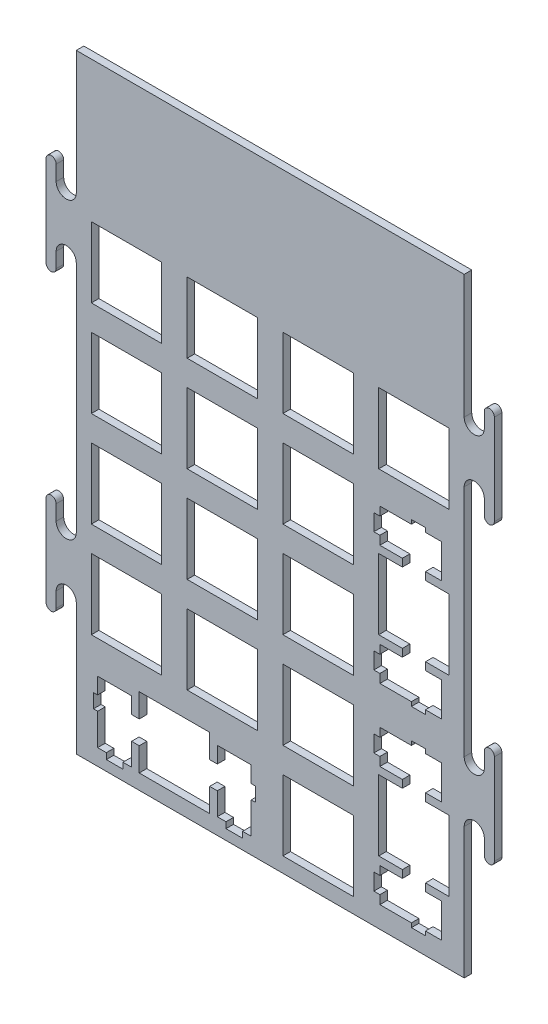
SolidWorks part; units mm, degrees
ref_plane "前视基准面" through (0, 0, 0) normal (0, 0, 1) x (1, 0, 0)
ref_plane "上视基准面" through (0, 0, 0) normal (0, 1, 0) x (1, 0, 0)
ref_plane "右视基准面" through (0, 0, 0) normal (1, 0, 0) x (0, 0, -1)
other "Configuration Table"
sketch "Model" plane through (0, 0, 0) normal (0, 0, 1) x (1, 0, 0)
  line L0 (114.6852, 14.7846) -> (114.6852, 10.0841)
  line L1 (114.6852, 10.0841) -> (113.1597, 10.0841)
  line L2 (113.1597, 10.0841) -> (113.1597, 13.3143)
  line L3 (113.1597, 13.3143) -> (106.4101, 13.3143)
  line L4 (106.4101, 13.3143) -> (106.4101, 10.0841)
  line L5 (106.4101, 10.0841) -> (105.5846, 10.0841)
  line L6 (105.5846, 10.0841) -> (105.5846, 7.2853)
  line L7 (105.5846, 7.2853) -> (106.4101, 7.2853)
  line L8 (106.4101, 7.2853) -> (106.4101, 1.0153)
  line L9 (106.4101, 1.0153) -> (108.1354, 1.0153)
  line L10 (108.1354, 1.0153) -> (108.1354, -0.185)
  line L11 (108.1354, -0.185) -> (111.4344, -0.185)
  line L12 (111.4344, -0.185) -> (111.4344, 1.0153)
  line L13 (111.4344, 1.0153) -> (113.1597, 1.0153)
  line L14 (113.1597, 1.0153) -> (113.1597, 5.4842)
  line L15 (113.1597, 5.4842) -> (114.6852, 5.4842)
  line L16 (114.6852, 5.4842) -> (114.6852, 0.7851)
  line L17 (114.6852, 0.7851) -> (128.6846, 0.7851)
  line L18 (128.6846, 0.7851) -> (128.6846, 5.4842)
  line L19 (128.6846, 5.4842) -> (130.2101, 5.4842)
  line L20 (130.2101, 5.4842) -> (130.2101, 1.0153)
  line L21 (130.2101, 1.0153) -> (131.9354, 1.0153)
  line L22 (131.9354, 1.0153) -> (131.9354, -0.185)
  line L23 (131.9354, -0.185) -> (135.2345, -0.185)
  line L24 (135.2345, -0.185) -> (135.2345, 1.0153)
  line L25 (135.2345, 1.0153) -> (136.9598, 1.0153)
  line L26 (136.9598, 1.0153) -> (136.9598, 7.2853)
  line L27 (136.9598, 7.2853) -> (137.7852, 7.2853)
  line L28 (137.7852, 7.2853) -> (137.7852, 10.0841)
  line L29 (137.7852, 10.0841) -> (136.9598, 10.0841)
  line L30 (136.9598, 10.0841) -> (136.9598, 13.3143)
  line L31 (136.9598, 13.3143) -> (130.2101, 13.3143)
  line L32 (130.2101, 13.3143) -> (130.2101, 10.0841)
  line L33 (130.2101, 10.0841) -> (128.6846, 10.0841)
  line L34 (128.6846, 10.0841) -> (128.6846, 14.7846)
  line L35 (128.6846, 14.7846) -> (114.6852, 14.7846)
  line L36 (143.2602, 14.7846) -> (157.2595, 14.7846)
  line L37 (157.2595, 14.7846) -> (157.2595, 0.7851)
  line L38 (157.2595, 0.7851) -> (143.2602, 0.7851)
  line L39 (143.2602, 0.7851) -> (143.2602, 14.7846)
  line L40 (168.8105, 33.4102) -> (168.8105, 32.5848)
  line L41 (168.8105, 32.5848) -> (162.5402, 32.5848)
  line L42 (162.5402, 32.5848) -> (162.5402, 30.8594)
  line L43 (162.5402, 30.8594) -> (161.3401, 30.8594)
  line L44 (161.3401, 30.8594) -> (161.3401, 27.5604)
  line L45 (161.3401, 27.5604) -> (162.5402, 27.5604)
  line L46 (162.5402, 27.5604) -> (162.5402, 25.8351)
  line L47 (162.5402, 25.8351) -> (167.0106, 25.8351)
  line L48 (167.0106, 25.8351) -> (167.0106, 24.3096)
  line L49 (167.0106, 24.3096) -> (162.3102, 24.3096)
  line L50 (162.3102, 24.3096) -> (162.3102, 10.3101)
  line L51 (162.3102, 10.3101) -> (167.0106, 10.3101)
  line L52 (167.0106, 10.3101) -> (167.0106, 8.7846)
  line L53 (167.0106, 8.7846) -> (162.5402, 8.7846)
  line L54 (162.5402, 8.7846) -> (162.5402, 7.0594)
  line L55 (162.5402, 7.0594) -> (161.3401, 7.0594)
  line L56 (161.3401, 7.0594) -> (161.3401, 3.7603)
  line L57 (161.3401, 3.7603) -> (162.5402, 3.7603)
  line L58 (162.5402, 3.7603) -> (162.5402, 2.035)
  line L59 (162.5402, 2.035) -> (168.8105, 2.035)
  line L60 (168.8105, 2.035) -> (168.8105, 1.2096)
  line L61 (168.8105, 1.2096) -> (171.6105, 1.2096)
  line L62 (171.6105, 1.2096) -> (171.6105, 2.035)
  line L63 (171.6105, 2.035) -> (174.8405, 2.035)
  line L64 (174.8405, 2.035) -> (174.8405, 8.7846)
  line L65 (174.8405, 8.7846) -> (171.6105, 8.7846)
  line L66 (171.6105, 8.7846) -> (171.6105, 10.3101)
  line L67 (171.6105, 10.3101) -> (176.3095, 10.3101)
  line L68 (176.3095, 10.3101) -> (176.3095, 24.3096)
  line L69 (176.3095, 24.3096) -> (171.6105, 24.3096)
  line L70 (171.6105, 24.3096) -> (171.6105, 25.8351)
  line L71 (171.6105, 25.8351) -> (174.8405, 25.8351)
  line L72 (174.8405, 25.8351) -> (174.8405, 32.5848)
  line L73 (174.8405, 32.5848) -> (171.6105, 32.5848)
  line L74 (171.6105, 32.5848) -> (171.6105, 33.4102)
  line L75 (171.6105, 33.4102) -> (168.8105, 33.4102)
  line L76 (105.1602, 33.8345) -> (119.1597, 33.8345)
  line L77 (119.1597, 33.8345) -> (119.1597, 19.8351)
  line L78 (119.1597, 19.8351) -> (105.1602, 19.8351)
  line L79 (105.1602, 19.8351) -> (105.1602, 33.8345)
  line L80 (124.2102, 33.8345) -> (138.2095, 33.8345)
  line L81 (138.2095, 33.8345) -> (138.2095, 19.8351)
  line L82 (138.2095, 19.8351) -> (124.2102, 19.8351)
  line L83 (124.2102, 19.8351) -> (124.2102, 33.8345)
  line L84 (143.2602, 33.8345) -> (157.2595, 33.8345)
  line L85 (157.2595, 33.8345) -> (157.2595, 19.8351)
  line L86 (157.2595, 19.8351) -> (143.2602, 19.8351)
  line L87 (143.2602, 19.8351) -> (143.2602, 33.8345)
  line L88 (105.1602, 52.8846) -> (119.1597, 52.8846)
  line L89 (119.1597, 52.8846) -> (119.1597, 38.8853)
  line L90 (119.1597, 38.8853) -> (105.1602, 38.8853)
  line L91 (105.1602, 38.8853) -> (105.1602, 52.8846)
  line L92 (124.2102, 52.8846) -> (138.2095, 52.8846)
  line L93 (138.2095, 52.8846) -> (138.2095, 38.8853)
  line L94 (138.2095, 38.8853) -> (124.2102, 38.8853)
  line L95 (124.2102, 38.8853) -> (124.2102, 52.8846)
  line L96 (143.2602, 52.8846) -> (157.2595, 52.8846)
  line L97 (157.2595, 52.8846) -> (157.2595, 38.8853)
  line L98 (157.2595, 38.8853) -> (143.2602, 38.8853)
  line L99 (143.2602, 38.8853) -> (143.2602, 52.8846)
  line L100 (168.8105, 71.5102) -> (168.8105, 70.6847)
  line L101 (168.8105, 70.6847) -> (162.5402, 70.6847)
  line L102 (162.5402, 70.6847) -> (162.5402, 68.9596)
  line L103 (162.5402, 68.9596) -> (161.3401, 68.9596)
  line L104 (161.3401, 68.9596) -> (161.3401, 65.6604)
  line L105 (161.3401, 65.6604) -> (162.5402, 65.6604)
  line L106 (162.5402, 65.6604) -> (162.5402, 63.935)
  line L107 (162.5402, 63.935) -> (167.0106, 63.935)
  line L108 (167.0106, 63.935) -> (167.0106, 62.4096)
  line L109 (167.0106, 62.4096) -> (162.3102, 62.4096)
  line L110 (162.3102, 62.4096) -> (162.3102, 48.4103)
  line L111 (162.3102, 48.4103) -> (167.0106, 48.4103)
  line L112 (167.0106, 48.4103) -> (167.0106, 46.8845)
  line L113 (167.0106, 46.8845) -> (162.5402, 46.8845)
  line L114 (162.5402, 46.8845) -> (162.5402, 45.1594)
  line L115 (162.5402, 45.1594) -> (161.3401, 45.1594)
  line L116 (161.3401, 45.1594) -> (161.3401, 41.8602)
  line L117 (161.3401, 41.8602) -> (162.5402, 41.8602)
  line L118 (162.5402, 41.8602) -> (162.5402, 40.1352)
  line L119 (162.5402, 40.1352) -> (168.8105, 40.1352)
  line L120 (168.8105, 40.1352) -> (168.8105, 39.3097)
  line L121 (168.8105, 39.3097) -> (171.6105, 39.3097)
  line L122 (171.6105, 39.3097) -> (171.6105, 40.1352)
  line L123 (171.6105, 40.1352) -> (174.8405, 40.1352)
  line L124 (174.8405, 40.1352) -> (174.8405, 46.8845)
  line L125 (174.8405, 46.8845) -> (171.6105, 46.8845)
  line L126 (171.6105, 46.8845) -> (171.6105, 48.4103)
  line L127 (171.6105, 48.4103) -> (176.3095, 48.4103)
  line L128 (176.3095, 48.4103) -> (176.3095, 62.4096)
  line L129 (176.3095, 62.4096) -> (171.6105, 62.4096)
  line L130 (171.6105, 62.4096) -> (171.6105, 63.935)
  line L131 (171.6105, 63.935) -> (174.8405, 63.935)
  line L132 (174.8405, 63.935) -> (174.8405, 70.6847)
  line L133 (174.8405, 70.6847) -> (171.6105, 70.6847)
  line L134 (171.6105, 70.6847) -> (171.6105, 71.5102)
  line L135 (171.6105, 71.5102) -> (168.8105, 71.5102)
  line L136 (105.1602, 71.9346) -> (119.1597, 71.9346)
  line L137 (119.1597, 71.9346) -> (119.1597, 57.9353)
  line L138 (119.1597, 57.9353) -> (105.1602, 57.9353)
  line L139 (105.1602, 57.9353) -> (105.1602, 71.9346)
  line L140 (124.2102, 71.9346) -> (138.2095, 71.9346)
  line L141 (138.2095, 71.9346) -> (138.2095, 57.9353)
  line L142 (138.2095, 57.9353) -> (124.2102, 57.9353)
  line L143 (124.2102, 57.9353) -> (124.2102, 71.9346)
  line L144 (143.2602, 71.9346) -> (157.2595, 71.9346)
  line L145 (157.2595, 71.9346) -> (157.2595, 57.9353)
  line L146 (157.2595, 57.9353) -> (143.2602, 57.9353)
  line L147 (143.2602, 57.9353) -> (143.2602, 71.9346)
  line L148 (105.1602, 90.9846) -> (119.1597, 90.9846)
  line L149 (119.1597, 90.9846) -> (119.1597, 76.9853)
  line L150 (119.1597, 76.9853) -> (105.1602, 76.9853)
  line L151 (105.1602, 76.9853) -> (105.1602, 90.9846)
  line L152 (124.2102, 90.9846) -> (138.2095, 90.9846)
  line L153 (138.2095, 90.9846) -> (138.2095, 76.9853)
  line L154 (138.2095, 76.9853) -> (124.2102, 76.9853)
  line L155 (124.2102, 76.9853) -> (124.2102, 90.9846)
  line L156 (143.2602, 90.9846) -> (157.2595, 90.9846)
  line L157 (157.2595, 90.9846) -> (157.2595, 76.9853)
  line L158 (157.2595, 76.9853) -> (143.2602, 76.9853)
  line L159 (143.2602, 76.9853) -> (143.2602, 90.9846)
  line L160 (162.3102, 90.9846) -> (176.3095, 90.9846)
  line L161 (176.3095, 90.9846) -> (176.3095, 76.9853)
  line L162 (176.3095, 76.9853) -> (162.3102, 76.9853)
  line L163 (162.3102, 76.9853) -> (162.3102, 90.9846)
  line L164 (102.1602, -2.2149) -> (102.1602, 23.8849)
  line L165 (179.3095, -2.2149) -> (179.3095, 23.8849)
  line L166 (179.3095, -2.2149) -> (102.1602, -2.2149)
  line L167 (102.1602, 118.9846) -> (179.3095, 118.9846)
  line L168 (96.1602, 79.3849) -> (96.1602, 97.3849)
  line L169 (98.1602, 97.3849) -> (98.1602, 94.3849)
  line L170 (98.1602, 79.3849) -> (98.1602, 82.3849)
  line L171 (102.1602, 94.3849) -> (102.1602, 118.9846)
  line L172 (102.1602, 35.8849) -> (102.1602, 82.3849)
  line L173 (179.3095, 35.8849) -> (179.3095, 82.3849)
  line L174 (179.3095, 35.8849) -> (179.3095, 82.3849)
  line L175 (179.3095, 118.9846) -> (179.3095, 94.3849)
  line L176 (185.3095, 79.3849) -> (185.3095, 97.3849)
  line L177 (183.3095, 97.3849) -> (183.3095, 94.3849)
  line L178 (183.3095, 79.3849) -> (183.3095, 82.3849)
  line L179 (96.1602, 38.8849) -> (96.1602, 20.8849)
  line L180 (98.1602, 20.8849) -> (98.1602, 23.8849)
  line L181 (98.1602, 38.8849) -> (98.1602, 35.8849)
  line L182 (185.3095, 38.8849) -> (185.3095, 20.8849)
  line L183 (183.3095, 20.8849) -> (183.3095, 23.8849)
  line L184 (183.3095, 38.8849) -> (183.3095, 35.8849)
  arc A0 (97.1602, 98.3849) -> (96.1602, 97.3849) centre (97.1602, 97.3849) ccw
  arc A1 (98.1602, 97.3849) -> (97.1602, 98.3849) centre (97.1602, 97.3849) ccw
  arc A2 (96.1602, 79.3849) -> (97.1602, 78.3849) centre (97.1602, 79.3849) ccw
  arc A3 (97.1602, 78.3849) -> (98.1602, 79.3849) centre (97.1602, 79.3849) ccw
  arc A4 (98.1602, 94.3849) -> (100.1602, 92.3849) centre (100.1602, 94.3849) ccw
  arc A5 (100.1602, 92.3849) -> (102.1602, 94.3849) centre (100.1602, 94.3849) ccw
  arc A6 (100.1602, 84.3849) -> (98.1602, 82.3849) centre (100.1602, 82.3849) ccw
  arc A7 (102.1602, 82.3849) -> (100.1602, 84.3849) centre (100.1602, 82.3849) ccw
  arc A8 (181.3095, 84.3849) -> (179.3095, 82.3849) centre (181.3095, 82.3849) ccw
  arc A9 (179.3095, 94.3849) -> (181.3095, 92.3849) centre (181.3095, 94.3849) ccw
  arc A10 (185.3095, 97.3849) -> (184.3095, 98.3849) centre (184.3095, 97.3849) ccw
  arc A11 (184.3095, 98.3849) -> (183.3095, 97.3849) centre (184.3095, 97.3849) ccw
  arc A12 (183.3095, 82.3849) -> (181.3095, 84.3849) centre (181.3095, 82.3849) ccw
  arc A13 (183.3095, 79.3849) -> (184.3095, 78.3849) centre (184.3095, 79.3849) ccw
  arc A14 (184.3095, 78.3849) -> (185.3095, 79.3849) centre (184.3095, 79.3849) ccw
  arc A15 (181.3095, 92.3849) -> (183.3095, 94.3849) centre (181.3095, 94.3849) ccw
  arc A16 (100.1602, 33.8849) -> (102.1602, 35.8849) centre (100.1602, 35.8849) ccw
  arc A17 (102.1602, 23.8849) -> (100.1602, 25.8849) centre (100.1602, 23.8849) ccw
  arc A18 (96.1602, 20.8849) -> (97.1602, 19.8849) centre (97.1602, 20.8849) ccw
  arc A19 (97.1602, 19.8849) -> (98.1602, 20.8849) centre (97.1602, 20.8849) ccw
  arc A20 (98.1602, 35.8849) -> (100.1602, 33.8849) centre (100.1602, 35.8849) ccw
  arc A21 (98.1602, 38.8849) -> (97.1602, 39.8849) centre (97.1602, 38.8849) ccw
  arc A22 (97.1602, 39.8849) -> (96.1602, 38.8849) centre (97.1602, 38.8849) ccw
  arc A23 (100.1602, 25.8849) -> (98.1602, 23.8849) centre (100.1602, 23.8849) ccw
  arc A24 (179.3095, 35.8849) -> (181.3095, 33.8849) centre (181.3095, 35.8849) ccw
  arc A25 (181.3095, 25.8849) -> (179.3095, 23.8849) centre (181.3095, 23.8849) ccw
  arc A26 (184.3095, 19.8849) -> (185.3095, 20.8849) centre (184.3095, 20.8849) ccw
  arc A27 (183.3095, 20.8849) -> (184.3095, 19.8849) centre (184.3095, 20.8849) ccw
  arc A28 (181.3095, 33.8849) -> (183.3095, 35.8849) centre (181.3095, 35.8849) ccw
  arc A29 (184.3095, 39.8849) -> (183.3095, 38.8849) centre (184.3095, 38.8849) ccw
  arc A30 (185.3095, 38.8849) -> (184.3095, 39.8849) centre (184.3095, 38.8849) ccw
  arc A31 (183.3095, 23.8849) -> (181.3095, 25.8849) centre (181.3095, 23.8849) ccw
extrude "凸台-拉伸1" add sketch "Model" along normal blind 1.5 contours A31 L183 A27 A26 L182 A30 A29 L184 A28 A24 L173 A8 A12 L178 A13 A14 L176 A10 A11 L177 A15 A9 L175 L167 L171 A5 A4 L169 A1 A0 L168 A2 A3 L170 A6 A7 L172 A16 A20 L181 A21 A22 L179 A18 A19 L180 A23 A17 L164 L166 L165 region at (140.8119, 66.9326, 0)
